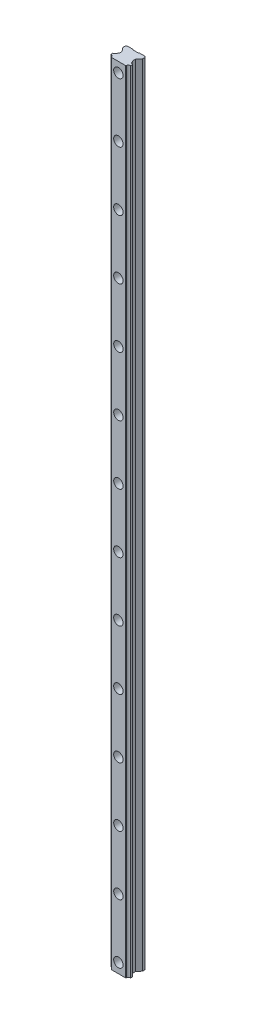
SolidWorks part; units mm, degrees
material "Nichtrostender Chromstahl"
ref_plane "Ebene vorne" through (0, 0, 0) normal (0, 0, 1) x (1, 0, 0)
ref_plane "Ebene oben" through (0, 0, 0) normal (0, 1, 0) x (1, 0, 0)
ref_plane "Ebene rechts" through (0, 0, 0) normal (1, 0, 0) x (0, 0, -1)
ref_plane "Ebene1" through (0, 0, 0) normal (0, 0, -1) x (-1, 0, 0)
sketch "Skizze1" plane through (0, 0, 0) normal (0, 0, -1) x (-1, 0, 0)
  line L0 (-10, 0) -> (10, 0)
  line L1 (10, 0) -> (10, 800)
  line L2 (10, 800) -> (-10, 800)
  line L3 (-10, 800) -> (-10, 0)
extrude "Aufsatz-Linear austragen1" add sketch "Skizze1" against normal blind 18
sketch "Skizze2" plane through (0, 0, 0) normal (0, -1, 0) x (1, 0, 0)
  line L0 (-2.5, 0) -> (2.5, 0)
  line L1 (2.5, 0) -> (2.5, 0.5)
  line L2 (2.5, 0.5) -> (-2.5, 0.5)
  line L3 (-2.5, 0.5) -> (-2.5, 0)
extrude "Schnitt-Linear austragen1" cut sketch "Skizze2" against normal through all
sketch "Skizze3" plane through (0, 0, 0) normal (0, -1, 0) x (1, 0, 0)
  line L0 (-10, 13.5) -> (-10, 7.5)
  line L1 (-10, 7.5) -> (-6.75, 7.5)
  line L2 (-6.75, 7.5) -> (-6.75, 10.5)
  line L3 (-6.75, 10.5) -> (-7.5, 11.1094)
  arc A0 (-7.5, 11.1094) -> (-10, 13.5) centre (-10, 10.9975) ccw
extrude "Schnitt-Linear austragen2" cut sketch "Skizze3" against normal through all
sketch "Skizze4" plane through (0, 0, 0) normal (0, -1, 0) x (1, 0, 0)
  line L0 (7.5, 11.1094) -> (6.75, 10.5)
  line L1 (6.75, 10.5) -> (6.75, 3.5)
  line L2 (6.75, 3.5) -> (10, 3.5)
  line L3 (10, 3.5) -> (10, 13.5)
  arc A0 (10, 13.5) -> (7.5, 11.1094) centre (10, 10.9975) ccw
extrude "Schnitt-Linear austragen3" cut sketch "Skizze4" against normal through all
draft "Formschräge1" type of draft neutral plane draft angle 50.906 faces to draft 1 face at (8.375, 400, 3.5) neutral plane through (10, 800, 18) neutral plane normal (1, 0, 0) parameters "D1"=50.906
draft "Formschräge2" type of draft neutral plane draft angle 50.906 faces to draft 1 face at (-8.375, 400, 7.5) neutral plane through (-6.75, 800, 7.5) neutral plane normal (-1, 0, 0) parameters "D1"=50.906
draft "Formschräge3" type of draft neutral plane draft angle 45 faces to draft 2 face at (2.5, 400, 0.25) face at (-2.5, 400, 0.25) neutral plane through (2.5, 800, 0.5) neutral plane normal (0, 0, -1) parameters "D1"=45
hole_wizard "Ø5.0 (5) Durchmesser Bohrung1" positions "Skizze6" profile "Skizze5" hole size "Ø5.0" standard "ANSI Metrisch"
sketch "Skizze6" plane through (0, 800, 0) normal (0, 1, 0) x (1, 0, 0)
  point P0 (10, -18)
sketch "Skizze5" plane through (10, 800, 18) normal (1, 0, 0) x (0, 0, 1)
  line L0 (0, 0) -> (0, 800)
  line L1 (0, 800) -> (2.5, 800)
  line L2 (2.5, 800) -> (2.5, 0)
  line L5 (2.5, 0) -> (0, 0)
  line L11 (0, -6.35) -> (0, 107.95) construction
  dimension "Bohrerdurchmesser" = 5
  dimension "Bohrungstiefe" = 800
hole_wizard "Ø5.0 (5) Durchmesser Bohrung2" positions "Skizze8" profile "Skizze7" hole size "Ø5.0" standard "ANSI Metrisch"
sketch "Skizze8" plane through (0, 0, 0) normal (0, -1, 0) x (-1, 0, 0)
  point P0 (10, -18)
sketch "Skizze7" plane through (-10, 0, 18) normal (1, 0, 0) x (0, 0, -1)
  line L0 (0, 0) -> (0, 800)
  line L1 (0, 800) -> (2.5, 800)
  line L2 (2.5, 800) -> (2.5, 0)
  line L5 (2.5, 0) -> (0, 0)
  line L11 (0, -6.35) -> (0, 107.95) construction
  dimension "Bohrerdurchmesser" = 5
  dimension "Bohrungstiefe" = 800
hole_wizard "Bohrung1" positions "Skizze10" profile "Skizze9" legacy
sketch "Skizze10" plane through (0, 0, 18) normal (0, 0, 1) x (1, 0, 0)
  point P0 (0, 790)
  point P1 (0, 730)
  point P2 (0, 670)
  point P3 (0, 610)
  point P4 (0, 550)
  point P5 (0, 490)
  point P6 (0, 430)
  point P7 (0, 370)
  point P8 (0, 310)
  point P9 (0, 250)
  point P10 (0, 190)
  point P11 (0, 130)
  point P12 (0, 70)
  point P13 (0, 10)
sketch "Skizze9" plane through (0, 790, 18) normal (1, 0, 0) x (0, -1, 0)
  line L0 (0, 0) -> (0, 18)
  line L1 (0, 18) -> (3, 18)
  line L2 (3, 18) -> (3, 8.5)
  line L3 (3, 8.5) -> (4.75, 8.5)
  line L4 (4.75, 8.5) -> (4.75, 0)
  line L5 (4.75, 0) -> (0, 0)
  line L6 (0, 110) -> (0, -10) construction
  dimension "Durchmesser" = 6
  dimension "Tiefe" = 18
  dimension "Senkdurchmesser1" = 9.5
  dimension "Senktiefe1" = 8.5
chamfer "Fase1" distance 1 angle 45 2 edges at (-10, 400, 0) (10, 400, 0)
chamfer "Fase2" distance 0.449 angle 42.13 2 edges at (-7.5, 400, 18) (7.5, 400, 18) first distance on face at (4.75, 790, 18)
